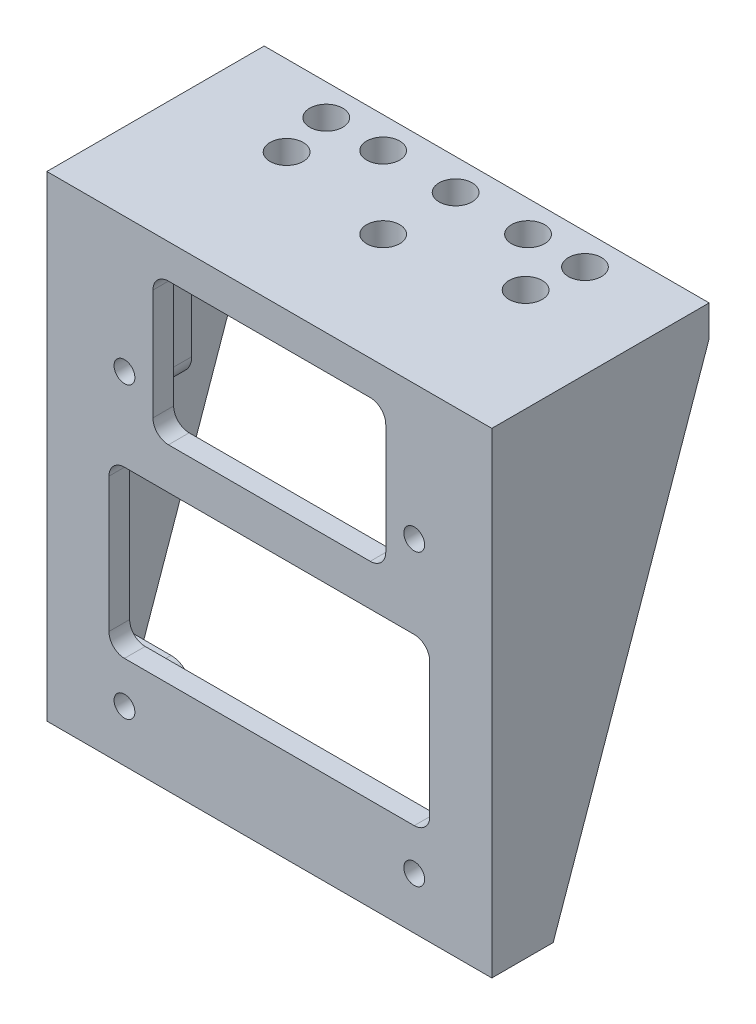
SolidWorks part; units mm, degrees
material "POM 乙缩醛共聚物"
ref_plane "Front" through (0, 0, 0) normal (0, 0, 1) x (1, 0, 0)
ref_plane "Top" through (0, 0, 0) normal (0, 1, 0) x (1, 0, 0)
ref_plane "Right" through (0, 0, 0) normal (1, 0, 0) x (0, 0, -1)
sketch "草图1" plane through (0, 0, 0) normal (0, 0, 1) x (1, 0, 0)
  line L0 (-6.3246, 3) -> (-10, 3) construction
  line L1 (21.5, -24.5) -> (-21.5, -24.5)
  line L2 (21.5, -24.5) -> (21.5, 24.5)
  line L3 (21.5, 24.5) -> (-21.5, 24.5)
  line L4 (-21.5, -24.5) -> (-21.5, 24.5)
  line L5 (21.5, -24.5) -> (-21.5, 24.5) construction
  line L6 (21.5, 24.5) -> (-21.5, -24.5) construction
  line L7 (14, -14) -> (-14, -14) construction
  line L8 (14, -14) -> (14, 14) construction
  line L9 (14, 14) -> (-14, 14) construction
  line L10 (-14, -14) -> (-14, 14) construction
  line L11 (14, -14) -> (-14, 14) construction
  line L12 (14, 14) -> (-14, -14) construction
  line L13 (10, -3) -> (6.3246, -3) construction
  line L14 (10, -3) -> (10, 3) construction
  line L15 (10, 3) -> (6.3246, 3) construction
  line L16 (-10, -3) -> (-10, 3) construction
  line L17 (10, -3) -> (-10, 3) construction
  line L18 (10, 3) -> (-10, -3) construction
  line L19 (-6.3246, -3) -> (-10, -3) construction
  circle A0 centre (-14, 14) radius 1.005
  circle A1 centre (14, 14) radius 1.005
  circle A2 centre (14, -14) radius 1.005
  circle A3 centre (-14, -14) radius 1.005
  arc A4 (6.3246, 3) -> (-6.3246, 3) centre (0, 0) ccw construction
  arc A5 (-6.3246, -3) -> (6.3246, -3) centre (0, 0) ccw construction
  point P0 (0, 0)
  point P6 (0, 0)
  dimension "D3" = 2.01
  dimension "D4" = 14
  dimension "D1" = 49
  dimension "D2" = 28
  dimension "D5" = 20
  dimension "D6" = 6
  dimension "D7" = 43
extrude "凸台-拉伸1" add sketch "草图1" along normal blind 2
sketch "草图2" plane through (0, 0, 0) normal (0, 0, -1) x (-1, 0, 0)
  line L0 (21.5, 24.5) -> (21.5, -24.5) construction
  line L1 (-21.5, 24) -> (21.5, 24)
  line L2 (-21.5, 24) -> (-21.5, 27)
  line L3 (-21.5, 27) -> (21.5, 27)
  line L4 (21.5, 24) -> (21.5, 27)
  line L5 (-21.5, 24) -> (21.5, 27) construction
  line L6 (-21.5, 27) -> (21.5, 24) construction
  line L8 (-21.5, -24.5) -> (-21.5, 24.5) construction
  line L9 (-21.5, 24.5) -> (21.5, 24.5) construction
  dimension "D1" = 3
  dimension "D2" = 0.5
extrude "凸台-拉伸2" add sketch "草图2" along normal blind 19 and the other way blind 2
sketch "草图4" plane through (0, 0, 0) normal (1, 0, 0) x (0, 0, -1)
  line L1 (19, 24) -> (0, 24)
  line L2 (0, 24) -> (0, -24.5)
  line L3 (0, -24.5) -> (2, -24.5)
  line L4 (2, -24.5) -> (19, 24)
  dimension "D1" = 2
extrude "凸台-拉伸3" add sketch "草图4" along normal blind 2 from surface starting at face at (-21.5, 8.8333, -5.6667)
extrude "凸台-拉伸5" add sketch "草图4<2>" against normal blind 2 from surface starting at face at (21.5, 8.8333, -5.6667)
sketch "草图4<2>" plane through (0, 0, 0) normal (1, 0, 0) x (0, 0, -1) same geometry as "草图4"
sketch "草图5" plane through (0, 24, 0) normal (0, -1, 0) x (1, 0, 0)
  line L0 (-21.5, -16) -> (21.5, -16) construction
  line L1 (19.5, -19) -> (-19.5, -19) construction
  line L2 (21.5, 0) -> (21.5, -19) construction
  line L3 (0, -17.8357) -> (0, 0) construction
  line L8 (-21.5, 0) -> (-21.5, -19) construction
  line L10 (11.5485, -11.2165) -> (-11.5485, -20.7835) construction
  circle A0 centre (-12.5, -16) radius 1.6
  circle A1 centre (12.5, -16) radius 1.6
  circle A2 centre (0, -16) radius 12.5 construction
  circle A3 centre (11.5485, -11.2165) radius 1.6
  circle A4 centre (-11.5485, -20.7835) radius 1.6 construction
  circle A5 centre (-11.5485, -11.2165) radius 1.6
  circle A6 centre (11.5485, -20.7835) radius 1.6 construction
  circle A7 centre (0, -16) radius 7 construction
  circle A8 centre (-7, -16) radius 1.6
  circle A9 centre (7, -16) radius 1.6
  circle A10 centre (0, -16) radius 1.6
  circle A11 centre (0, -9) radius 1.6
  point P23 (0, -16)
  dimension "D2" = 3.2
  dimension "D5" = 14
  dimension "D6" = 3.2
  dimension "D7" = 3.2
  dimension "D1" = 25
  dimension "D3" = 3
  dimension "D4" = 22.5
extrude "切除-拉伸1" cut sketch "草图5" against normal through all
sketch "草图8" plane through (0, 0, 0) normal (0, 0, -1) x (-1, 0, 0)
  line L0 (19.5, 24) -> (-19.5, 24) construction
  line L1 (11.25, 20) -> (11.25, 23.7)
  line L2 (11.25, 23.7) -> (-0.75, 23.7)
  line L7 (-11.25, 10) -> (11.25, 10)
  line L8 (11.25, 10) -> (11.25, 20)
  line L9 (-0.75, 23.7) -> (-11.25, 23.7)
  line L10 (-11.25, 10) -> (-11.25, 23.7)
  line L11 (-19.5, 24) -> (-19.5, -24.5) construction
  line L12 (-15.5, -10) -> (15.5, -10)
  line L13 (-15.5, -10) -> (-15.5, 6)
  line L14 (-15.5, 6) -> (15.5, 6)
  line L15 (15.5, -10) -> (15.5, 6)
  line L16 (-15.5, -10) -> (15.5, 6) construction
  line L17 (-15.5, 6) -> (15.5, -10) construction
  circle A3 centre (-14, -14) radius 1.005 construction
  circle A4 centre (14, -14) radius 1.005 construction
  point P8 (0, -2)
  dimension "D1" = 24
  dimension "D4" = 2.75
  dimension "D6" = 4
  dimension "D3" = 2.75
  dimension "D5" = 4
  dimension "D7" = 4
  dimension "D8" = 12
  dimension "D9" = 0.3
extrude "切除-拉伸3" cut sketch "草图8" against normal through all and the other way through all
sketch "草图12" plane through (0, 0, 0) normal (0, 0, -1) x (-1, 0, 0)
  line L0 (12, -14) -> (12, -24.5)
  line L1 (19.5, -24.5) -> (-19.5, -24.5) construction
  line L2 (12, -24.5) -> (19.5, -24.5)
  line L3 (19.5, -24.5) -> (19.5, -12)
  line L4 (19.5, 24) -> (19.5, -24.5) construction
  line L5 (19.5, -12) -> (14, -12)
  line L6 (0, 0) -> (0, -8.5523) construction
  line L7 (-19.5, -12) -> (-14, -12)
  line L8 (-19.5, -24.5) -> (-19.5, -12)
  line L9 (-12, -24.5) -> (-19.5, -24.5)
  line L10 (-12, -14) -> (-12, -24.5)
  line L11 (14, 12) -> (19.5, 12)
  line L13 (19.5, 12) -> (19.5, 24)
  line L14 (19.5, 24) -> (12, 24)
  line L15 (-19.5, 24) -> (19.5, 24) construction
  line L16 (12, 24) -> (12, 14)
  line L17 (-12, 24) -> (-12, 14)
  line L18 (-19.5, 24) -> (-12, 24)
  line L19 (-19.5, 12) -> (-19.5, 24)
  line L20 (-14, 12) -> (-19.5, 12)
  arc A0 (14, -12) -> (12, -14) centre (14, -14) ccw
  arc A1 (-14, -12) -> (-12, -14) centre (-14, -14) cw
  arc A2 (12, 14) -> (14, 12) centre (14, 14) ccw
  arc A3 (-12, 14) -> (-14, 12) centre (-14, 14) cw
  circle A4 centre (14, 14) radius 1.005 construction
  circle A5 centre (-14, 14) radius 1.005 construction
  circle A6 centre (-14, -14) radius 1.005 construction
  circle A7 centre (14, -14) radius 1.005 construction
  circle A8 centre (14, 14) radius 1.005
  circle A9 centre (-14, 14) radius 1.005
  circle A10 centre (-14, -14) radius 1.005
  circle A11 centre (14, -14) radius 1.005
  dimension "D1" = 4
  dimension "D2" = 4
extrude "凸台-拉伸6" add sketch "草图12" along normal blind 2.5
sketch "草图13" plane through (0, 0, 2) normal (0, 0, 1) x (1, 0, 0)
  line L0 (-21.5, 27) -> (-21.5, -24.5) construction
  line L1 (21.5, -24.5) -> (-21.5, -24.5)
  line L2 (21.5, -24.5) -> (21.5, -19)
  line L3 (21.5, -19) -> (-21.5, -19)
  line L4 (-21.5, -24.5) -> (-21.5, -19)
  dimension "D1" = 5.5
extrude "切除-拉伸4" cut sketch "草图13" against normal through all
fillet "圆角1" radius 1.5 16 edges at (19.5, 24, -10.75) (19.5, -12, -1.25) (19.5, 12, -1.25) (-11.25, 10, 1) (11.25, 10, 1) (-11.25, 23.7, 1) (11.25, 23.7, 1) (-19.5, 24, -10.75) (-19.5, 12, -1.25) (-19.5, -12, -1.25) (15.5, -10, 1) (15.5, 6, 1) (-15.5, 6, 1) (-15.5, -10, 1) (12, 24, -1.25) (-12, 24, -1.25)
